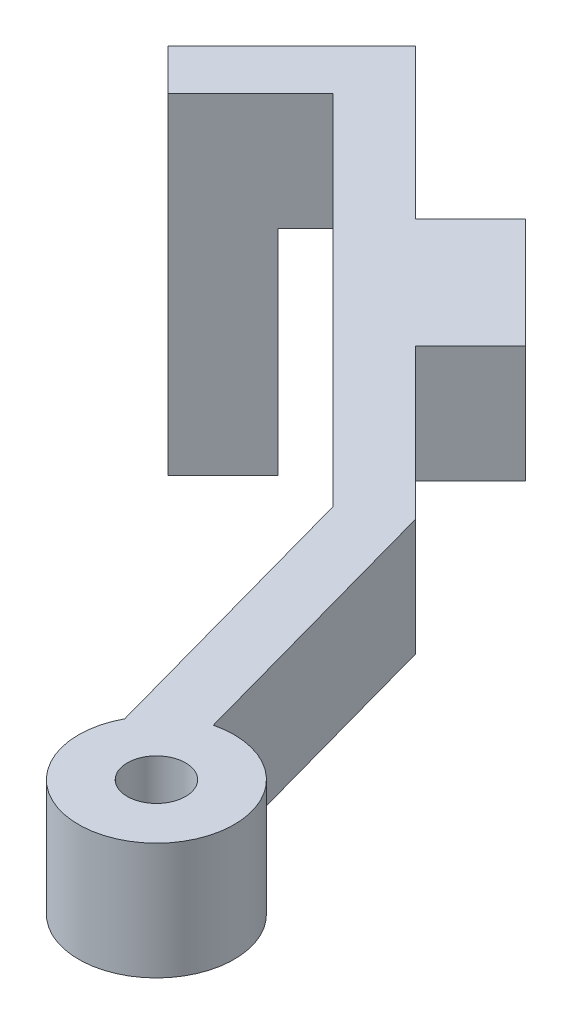
SolidWorks part; units mm, degrees
ref_plane "Front Plane" through (0, 0, 0) normal (0, 0, 1) x (1, 0, 0)
ref_plane "Top Plane" through (0, 0, 0) normal (0, 1, 0) x (1, 0, 0)
ref_plane "Right Plane" through (0, 0, 0) normal (1, 0, 0) x (0, 0, -1)
sketch "Sketch1" plane through (0, 0, 0) normal (0, 1, 0) x (1, 0, 0)
  circle A3 centre (0, -38.254) radius 38.254 construction
  circle A4 centre (0, -40.254) radius 40.254 construction
  circle A5 centre (0, -45.254) radius 45.254 construction
  dimension "D1" = 90.508
  dimension "D2" = 80.508
  dimension "D3" = 76.508
sketch "Sketch3" plane through (0, 0, 0) normal (0, 1, 0) x (1, 0, 0)
  line L8 (58.3717, -39.6268) -> (0, 18.7448)
  line L9 (0, 18.7448) -> (-58.3717, -39.6268)
  line L10 (-58.3717, -39.6268) -> (58.3717, -39.6268) construction
  line L17 (58.3717, -39.6268) -> (73.025, -92.6112)
  line L23 (73.025, -92.6112) -> (82.55, -92.6112)
  line L25 (66.8826, -34.6674) -> (80.2733, -83.0862)
  line L26 (66.8826, -34.6674) -> (0, 32.2152)
  line L27 (0, 32.2152) -> (-65.1069, -32.8917)
  line L28 (-65.1069, -32.8917) -> (-58.3717, -39.6268)
  line L30 (80.2733, -83.0862) -> (82.55, -83.0862) construction
  line L31 (80.2733, -83.0862) -> (82.55, -92.6112)
  line L32 (-20.2056, 12.0096) -> (-13.4704, 5.2744)
  circle A3 centre (0, -45.254) radius 45.254 construction
  dimension "D1" = 45
  dimension "D2" = 45
  dimension "D4" = 52.9844
  dimension "D5" = 9.525
  dimension "D7" = 82.55
  dimension "D3" = 82.55
  dimension "D8" = 63.5
  dimension "D6" = 9.525
extrude "Boss-Extrude1" add sketch "Sketch3" along normal blind 19.05 from offset 44.45 contours L27 L32 L9 L8 L17 L23 L31 L25 L26 region at (30.3291, 0, 9.2978)
sketch "Sketch26" plane through (0, 63.5, 0) normal (0, 1, 0) x (1, 0, 0)
  circle A0 centre (82.55, -92.6112) radius 12.7
  circle A1 centre (82.55, -92.6112) radius 4.7625
  line M11 (73.025, -92.6112) -> (82.55, -92.6112)
  line M12 (82.55, -92.6112) -> (80.2733, -83.0862)
  dimension "D1" = 25.4
  dimension "D2" = 9.525
extrude "Boss-Extrude7" add sketch "Sketch26" against normal up to surface (19.05 mm away) contours A0 up to face at (36.3807, 44.45, 30.4843)
extrude "Cut-Extrude6" cut sketch "Sketch26<3>" against normal through all contours A1 M11 M12 | A1 M12 M11 region at (83.1742, 63.5, 93.1038) region at (80.2389, 63.5, 90.7875)
sketch "Sketch26<3>" plane through (0, 63.5, 0) normal (0, 1, 0) x (1, 0, 0) same geometry as "Sketch26"
sketch "Sketch28" plane through (0, 44.45, 0) normal (0, -1, 0) x (1, 0, 0)
  line L0 (-4.4901, -14.2547) -> (-11.2253, -20.9899)
  line L1 (0, -32.2152) -> (-20.2056, -12.0096) construction
  line L2 (-11.2253, -20.9899) -> (-20.2056, -12.0096)
  line L3 (-20.2056, -12.0096) -> (-13.4704, -5.2744)
  line L4 (-13.4704, -5.2744) -> (-4.4901, -14.2547)
  dimension "D1" = 12.7
extrude "Boss-Extrude8" add sketch "Sketch28" along normal blind 34.925
sketch "Sketch29" plane through (0, 63.5, 0) normal (0, 1, 0) x (1, 0, 0)
  line L0 (42.4216, -10.2064) -> (51.4018, -1.2261)
  line L1 (66.8826, -34.6674) -> (0, 32.2152) construction
  line L2 (51.4018, -1.2261) -> (33.4413, 16.7344)
  line L3 (33.4413, 16.7344) -> (24.4611, 7.7541)
  line L4 (24.4611, 7.7541) -> (42.4216, -10.2064)
  point P4 (33.4413, -1.2261)
  dimension "D1" = 25.4
  dimension "D2" = 12.7
extrude "Boss-Extrude9" add sketch "Sketch29" against normal up to surface (19.05 mm away) up to face at (82.55, 44.45, 97.3737)
equation "\"tightTol\" = 0.005in"
equation "\"normTol\" = 0.01in"
equation "\"looseTol\" = 0.02in"
equation "\"D1@Sketch1\"=\"looseTol\"+9cm"
equation "\"D2@Sketch1\"=8cm+\"looseTol\""
equation "\"D3@Sketch1\"=7.6cm+\"looseTol\""
equation "\"D2\"= 0.875 - 10.7mm"
equation "\"D1\"= 10.7mm"
equation "\"D1@Boss-Extrude1\"=40mm"
equation "\"D19@Boss-Extrude2\"=0.250000-1.5*\"normTol\""
equation "\"D4@Sketch3\"= 4.95 - 2.864"
